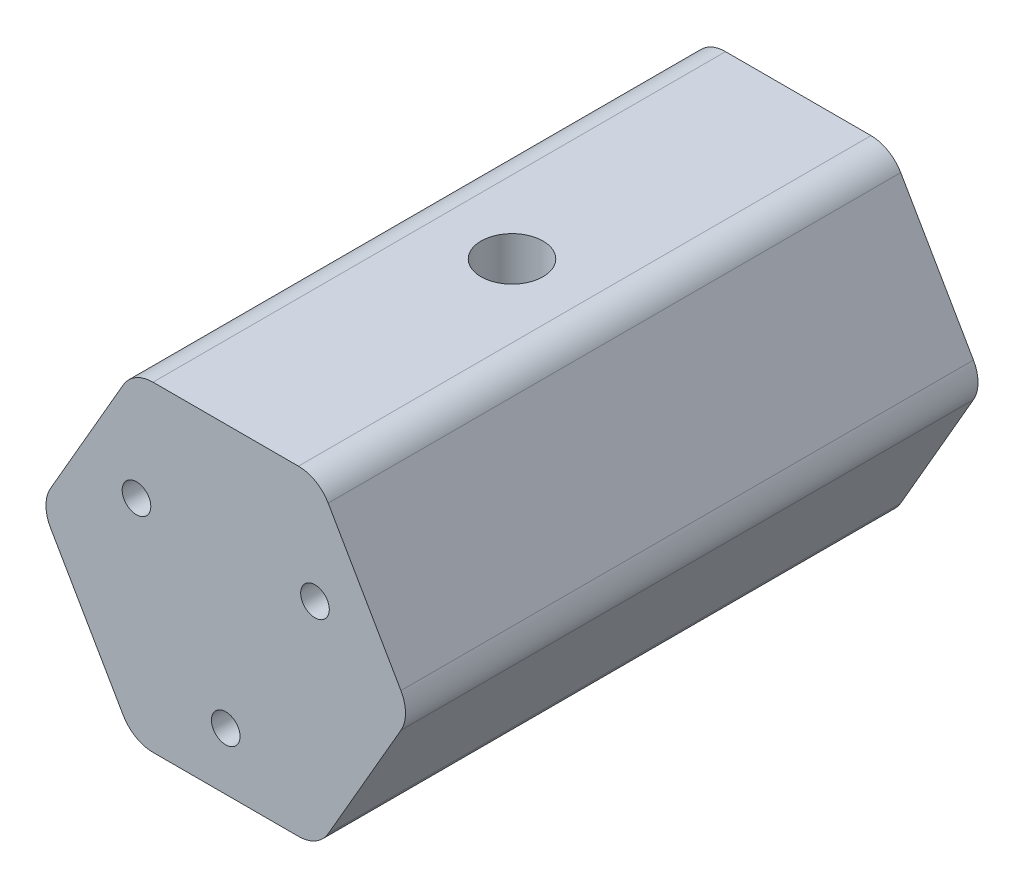
SolidWorks part; units mm, degrees
material "6061-T6 (SS)"
ref_plane "Front Plane" through (0, 0, 0) normal (0, 0, 1) x (1, 0, 0)
ref_plane "Top Plane" through (0, 0, 0) normal (0, 1, 0) x (1, 0, 0)
ref_plane "Right Plane" through (0, 0, 0) normal (1, 0, 0) x (0, 0, -1)
sketch "Sketch1" plane through (0, 0, 0) normal (0, 0, 1) x (1, 0, 0)
  line L7 (-6.3509, -14) -> (6.3509, -14)
  line L8 (8.9489, -12.5) -> (15.2998, -1.5)
  line L9 (15.2998, 1.5) -> (8.9489, 12.5)
  line L10 (6.3509, 14) -> (-6.3509, 14)
  line L11 (-8.9489, 12.5) -> (-15.2998, 1.5)
  line L12 (-15.2998, -1.5) -> (-8.9489, -12.5)
  circle A0 centre (0, 0) radius 9 construction
  circle A1 centre (-7.7942, 4.5) radius 1.25
  circle A2 centre (7.7942, 4.5) radius 1.25
  circle A3 centre (0, -9) radius 1.25
  circle A4 centre (0, 0) radius 14 construction
  arc A5 (-6.3509, -14) -> (-8.9489, -12.5) centre (-6.3509, -11) cw
  arc A6 (6.3509, -14) -> (8.9489, -12.5) centre (6.3509, -11) ccw
  arc A8 (15.2998, -1.5) -> (15.2998, 1.5) centre (12.7017, 0) ccw
  arc A9 (8.9489, 12.5) -> (6.3509, 14) centre (6.3509, 11) ccw
  arc A10 (-6.3509, 14) -> (-8.9489, 12.5) centre (-6.3509, 11) ccw
  arc A11 (-15.2998, 1.5) -> (-15.2998, -1.5) centre (-12.7017, 0) ccw
  circle A12 centre (0, 0) radius 9 construction
  point P11 (0, 0)
  point P23 (16.1658, 0)
  dimension "D1" = 3
  dimension "D2" = 2.5
  dimension "D3" = 5
  dimension "D4" = 3
extrude "Boss-Extrude1" add sketch "Sketch1" along normal blind 50
sketch "Sketch3" plane through (0, 14, 0) normal (0, 1, 0) x (1, 0, 0)
  line L0 (0, 0) -> (0, -50) construction
  line L1 (6.3509, -50) -> (-6.3509, -50) construction
  point P0 (0, -25)
hole_wizard "1/4-28 Tapped Hole1" positions "Sketch3" profile "Sketch4" tap size "1/4-28" standard "ANSI Inch" end condition through all
cosmetic thread "Hole Thread1" parameters "D2"=6.35
sketch "Sketch4" plane through (0, 14, 25) normal (1, 0, 0) x (0, 0, 1)
  line L0 (0, 0) -> (0, 28)
  line L1 (0, 28) -> (2.7051, 28)
  line L2 (2.7051, 28) -> (2.7051, 0)
  line L5 (2.7051, 0) -> (0, 0)
  line L11 (0, -6.35) -> (0, 107.95) construction
  dimension "Thru Tap Drill Dia." = 5.4102
  dimension "Thru Tap Drill Depth" = 28
equation "\"D1@Boss-Extrude1\"=\"Strut Length@Rocker Bogie Assy.Assembly\""
